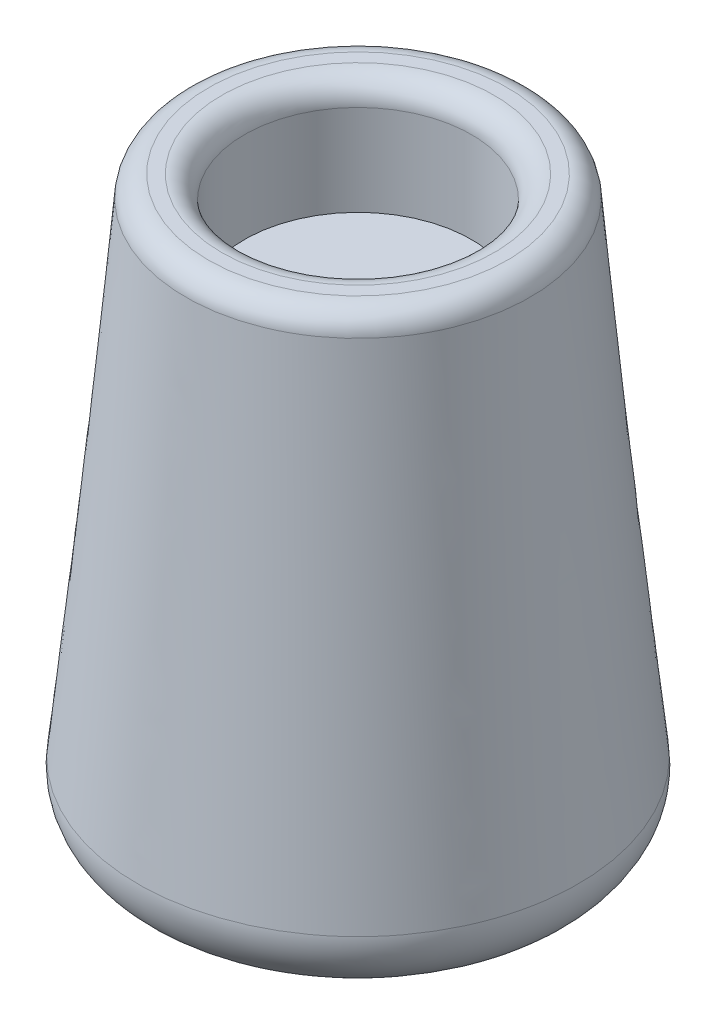
SolidWorks part; units mm, degrees
material "Silicon Rubber"
ref_plane "Front Plane" through (0, 0, 0) normal (0, 0, 1) x (1, 0, 0)
ref_plane "Top Plane" through (0, 0, 0) normal (0, 1, 0) x (1, 0, 0)
ref_plane "Right Plane" through (0, 0, 0) normal (1, 0, 0) x (0, 0, -1)
ref_plane "Plane1" through (0, 50, 0) normal (0, 1, 0) x (1, 0, 0)
sketch "Sketch1" plane through (0, 0, 0) normal (0, 1, 0) x (1, 0, 0)
  circle A0 centre (0, 0) radius 20
  dimension "D1" = 40
sketch "Sketch2" plane through (0, 50, 0) normal (0, 1, 0) x (1, 0, 0)
  circle A0 centre (0, 0) radius 15
  dimension "D1" = 30
loft "Loft1" add profiles "Sketch2", "Sketch1" connector at (-10.494, 50, -10.718) connector at (-17.4368, 0, -9.7958)
sketch "Sketch3" plane through (0, 50, 0) normal (0, 1, 0) x (1, 0, 0)
  circle A0 centre (0, 0) radius 10
  dimension "D1" = 20
extrude "Cut-Extrude1" cut sketch "Sketch3" against normal blind 10 and the other way through all
fillet "Fillet4" radius 5 1 edges at (0, 0, 20)
fillet "Fillet5" radius 2 2 edges at (0, 50, 15) (0, 50, 10)
